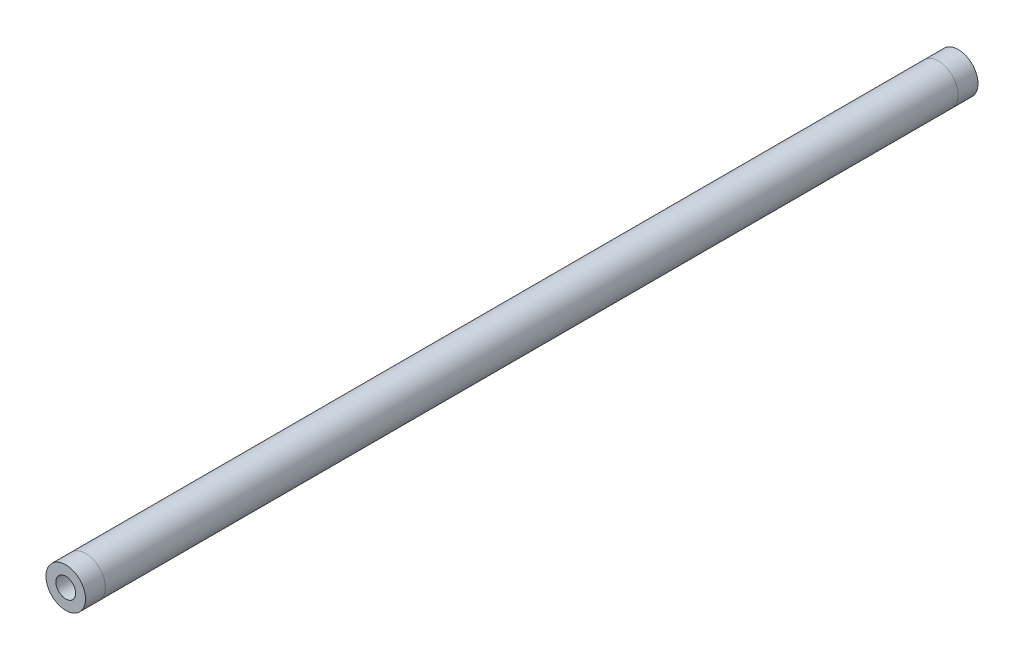
SolidWorks part; units mm, degrees
ref_plane "Front Plane" through (0, 0, 0) normal (0, 0, 1) x (1, 0, 0)
ref_plane "Top Plane" through (0, 0, 0) normal (0, 1, 0) x (1, 0, 0)
ref_plane "Right Plane" through (0, 0, 0) normal (1, 0, 0) x (0, 0, -1)
sketch "Axis" plane through (0, 0, 0) normal (1, 0, 0) x (0, 0, -1)
  line L0 (0, 0) -> (286.4311, 0) construction
  line L1 (286.4311, 0) -> (280.0811, 0)
  line L2 (286.4311, 0) -> (308.3259, 0) construction
  line L3 (0, 0) -> (-21.8948, 0) construction
  point P4 (0, 0)
  point P5 (286.4311, 0)
  point P6 (280.0811, 0)
  dimension "D1" = 6.35
  dimension "D2" = 21.8948
  dimension "D3" = 21.8948
sketch "Sketch1" plane through (0, 0, 0) normal (0, 0, 1) x (1, 0, 0)
  circle A0 centre (0, 0) radius 6.35
  circle A1 centre (0, 0) radius 4.826
  circle A2 centre (0, 0) radius 3.175
  dimension "D1" = 12.7
  dimension "D2" = 1.524
  dimension "D3" = 6.35
extrude "Threaded insert 1-1" add sketch "Sketch1" against normal blind 6.35 contours A0 A1 | A1 A2 region at (-6.1704, 0, 0) region at (-4.6895, 0, 0)
extrude "Threaded insert 1-2" add sketch "Sketch1<3>" against normal blind 9.525 from surface contours A1 A2 region at (-4.6895, 0, 0) starting at face at (6.35, 0, -6.35)
sketch "Sketch1<3>" plane through (0, 0, 0) normal (0, 0, 1) x (1, 0, 0) same geometry as "Sketch1"
extrude "Tube extrude" add sketch "Sketch1<4>" against normal up to vertex (280.0811 mm away) from surface separate body contours A0 A1 region at (-6.1704, 0, 0) up to point (0, 0, -280.0811) starting at face at (4.826, 0, -6.35)
sketch "Sketch1<4>" plane through (0, 0, 0) normal (0, 0, 1) x (1, 0, 0) same geometry as "Sketch1"
extrude "Threaded insert 2-1" add sketch "Sketch1<6>" along normal blind 9.525 from surface separate body contours A1 A2 region at (-4.6895, 0, 0) starting at face at (4.826, 0, -280.0811)
sketch "Sketch1<6>" plane through (0, 0, 0) normal (0, 0, 1) x (1, 0, 0) same geometry as "Sketch1"
extrude "Threaded insert 2-2" add sketch "Sketch1<9>" against normal blind 6.35 from surface separate body contours A1 A2 | A0 A1 region at (-6.1704, 0, 0) region at (-4.6895, 0, 0) starting at face at (4.826, 0, -280.0811)
sketch "Sketch1<9>" plane through (0, 0, 0) normal (0, 0, 1) x (1, 0, 0) same geometry as "Sketch1"
combine bodies "Combine1" operation type add bodies to combine 106 104
equation "\"Threaded insert outer thickness\"= .25"
equation "\"D1@Threaded insert 1-1\"=\"Threaded insert outer thickness\""
equation "\"D1@Threaded insert 2-2\"=\"Threaded insert outer thickness\""
equation "\"D1@Axis\" = \"Threaded insert outer thickness\""
